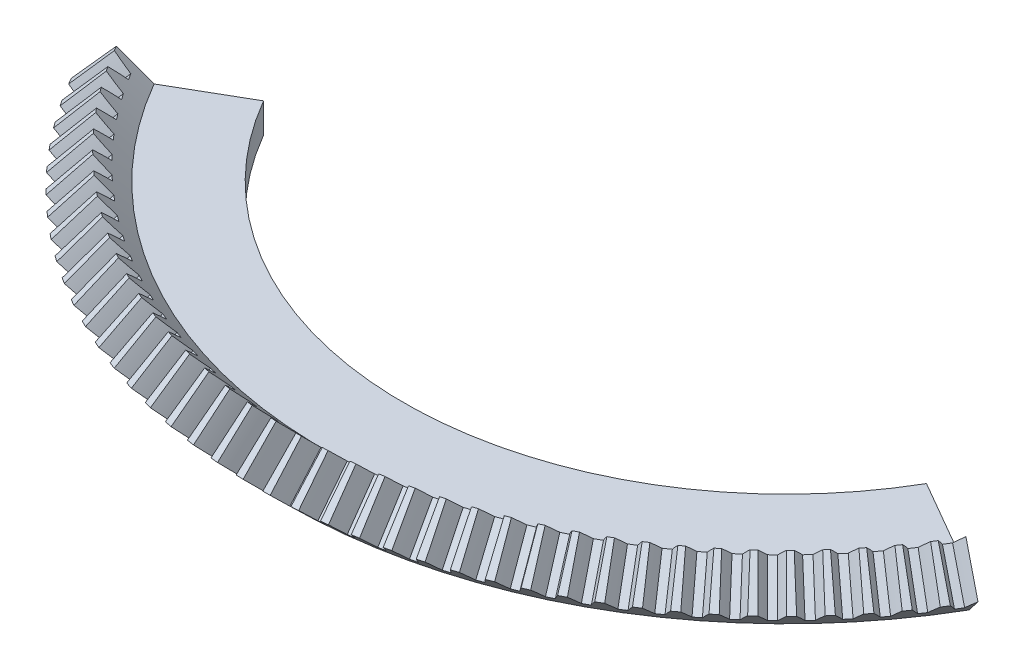
SolidWorks part; units mm, degrees
ref_plane "Front Plane" through (0, 0, 0) normal (0, 0, 1) x (1, 0, 0)
ref_plane "Top Plane" through (0, 0, 0) normal (0, 1, 0) x (1, 0, 0)
ref_plane "Right Plane" through (0, 0, 0) normal (1, 0, 0) x (0, 0, -1)
sketch "Sketch11" plane through (0, 0, 0) normal (0, 0, 1) x (1, 0, 0)
  line L0 (0, 0) -> (0, 120) construction
  line L1 (0, 0) -> (-90, 0) construction
  line L2 (0, 0) -> (0, -49.4819) construction
  line L3 (0, -49.4819) -> (-91.0605, -49.4819) construction
  line L4 (0, -79.9822) -> (-88.82, -79.9822) construction
  line L5 (-90, 120) -> (0.0147, 210.0147) construction
  line L6 (-90, 120) -> (-61.5021, 120) construction
  line L7 (0.0147, 210.0147) -> (-96.0377, 116.1829) construction
  line L8 (0.0147, 210.0147) -> (-92.7643, 115.0069) construction
  line L9 (0.0147, 210.0147) -> (0.0147, 146.7224) construction
  line L10 (-90, 120) -> (-88.9191, 118.9445)
  line L11 (-90, 120) -> (-91.0402, 121.0648)
  line L12 (-91.0402, 121.0648) -> (-85.3176, 126.6551)
  line L13 (-85.3176, 126.6551) -> (-83.3068, 124.6916)
  line L14 (-83.3068, 124.6916) -> (-88.9191, 118.9445)
  line L15 (-88.9191, 118.9445) -> (-81.7646, 111.9578)
  line L16 (-81.7646, 111.9578) -> (0, 111.9578)
  line L17 (-83.3068, 124.6916) -> (-78.6153, 120)
  line L18 (-78.6153, 120) -> (0, 120)
  line L19 (0, 120) -> (0, 111.9578)
  dimension "D1" = 90
  dimension "D2" = 91.0605
  dimension "D3" = 88.82
  dimension "D4" = 45
  dimension "D5" = 127.3
  dimension "D6" = 45.67
  dimension "D7" = 44.32
revolve "Revolve1" add sketch "Sketch11" angle 360 about L0
sketch "Sketch12" plane through (0, 0, 0) normal (1, 0, 0) x (0, 0, -1)
  line L0 (-88.9191, 118.9445) -> (0, 207.8636) construction
  line L1 (0, 111.9578) -> (0, 207.8636) construction
  line L2 (-81.7646, 111.9578) -> (81.7646, 111.9578) construction
  line L3 (-88.9191, 118.9445) -> (22.2775, 118.9445) construction
  line L4 (88.9191, 118.9445) -> (-88.9191, 118.9445) construction
  dimension "D1" = 45
sketch "Sketch13" plane through (0, 111.9578, 0) normal (0, -1, 0) x (1, 0, 0)
  line L0 (0, 81.7646) -> (-67.0377, 81.7646) construction
  circle A0 centre (0, 0) radius 81.7646 construction
ref_plane "Plane2" through (0, 16.4367, -16.0511) normal (0, 0.7154, -0.6987) x (1, 0, 0)
sketch "Sketch14" plane through (0, 16.4367, -16.0511) normal (0, 0.7154, -0.6987) x (1, 0, 0)
  arc A1 (-1.0406, -143.4694) -> (0, -146.7194) centre (40.9134, -131.8281) ccw
  arc A2 (-2.2935, -143.4526) -> (-3.4211, -146.6734) centre (-43.9195, -130.688) cw
  arc A3 (-3.4211, -146.6734) -> (0, -146.7194) centre (0, -19.4194) ccw
  arc A4 (-2.2935, -143.4526) -> (-1.0406, -143.4694) centre (0, -19.4194) ccw
  point P1 (0, 0)
ref_plane "Plane3" through (0, 107.5134, -104.9912) normal (0, 0.7154, -0.6987) x (1, 0, 0)
sketch "Sketch15" plane through (0, 107.5134, -104.9912) normal (0, 0.7154, -0.6987) x (1, 0, 0)
  circle A0 centre (0, -145.2557) radius 0.05
extrude "Cut-Extrude1" cut sketch "Sketch14" along normal blind 12
pattern_circular "CirPattern1" count 120 over 360 about axis through (0, 118.9445, 0) along (0, -1, 0) of "Cut-Extrude1"
sketch "Sketch17" plane through (0, 111.9578, 0) normal (0, -1, 0) x (1, 0, 0)
  circle A0 centre (0, 0) radius 90
extrude "Cut-Extrude4" cut sketch "Sketch17" against normal blind 3
sketch "Sketch18" plane through (0, 120, 0) normal (0, 1, 0) x (1, 0, 0)
  line L0 (-78.6153, 0) -> (99.4644, 0)
  line L1 (99.4644, 0) -> (99.4644, 123.9381)
  line L2 (99.4644, 123.9381) -> (-125.0006, 123.9381)
  line L3 (-125.0006, 123.9381) -> (-125.0006, 0)
  line L4 (-125.0006, 0) -> (-78.6153, 0)
  circle A0 centre (0, 0) radius 78.6153 construction
extrude "Cut-Extrude8" cut sketch "Sketch18" against normal blind 42 and the other way blind 74
sketch "Sketch20" plane through (0, 120, 0) normal (0, 1, 0) x (1, 0, 0)
  circle A0 centre (0, 0) radius 65
extrude "Cut-Extrude9" cut sketch "Sketch20" against normal blind 42
sketch "Sketch21" plane through (0, 120, 0) normal (0, 1, 0) x (1, 0, 0)
  line L0 (0, 0) -> (-94.2687, -54.4261)
  line L2 (0, 0) -> (-43.355, 0) construction
  line L3 (0, 0) -> (40.0116, 0) construction
  line L4 (-94.2687, -54.4261) -> (-137.9055, 21.155)
  line L5 (-137.9055, 21.155) -> (-72.4742, 58.9318)
  line L6 (-72.4742, 58.9318) -> (-28.8374, -16.6493)
  arc M1 (65, 0) -> (-65, 0) centre (0, 0) cw
  line M2 (-65, 0) -> (-78.6153, 0)
  arc M3 (-78.6153, 0) -> (78.6153, 0) centre (0, 0) ccw
  dimension "D1" = 30
extrude "Cut-Extrude11" cut sketch "Sketch21" along normal blind 47 and the other way blind 67 contours L6 L5 L4 L0 M3 M2 M1
sketch "Sketch22" plane through (0, 120, 0) normal (0, 1, 0) x (1, 0, 0)
  line L0 (24.3569, -14.0625) -> (93.3239, -53.8806)
  line L1 (0, 0) -> (44.0283, 0) construction
  line L2 (93.3239, -53.8806) -> (124.2396, -8.7618)
  line L3 (124.2396, -8.7618) -> (58.741, 36.1182)
  line L4 (58.741, 36.1182) -> (24.3569, -14.0625)
  dimension "D1" = 30
extrude "Cut-Extrude13" cut sketch "Sketch22" along normal blind 34 and the other way blind 56
sketch "Sketch23" plane through (0, 120, 0) normal (0, 1, 0) x (1, 0, 0)
  line L0 (-38.7517, -22.3733) -> (-92.4341, -53.3668)
  line L1 (0, 0) -> (-27.7753, 0) construction
  line L2 (-92.4341, -53.3668) -> (-128.3692, 8.8746)
  line L3 (-128.3692, 8.8746) -> (-70.1997, 38.7855)
  line L4 (-70.1997, 38.7855) -> (-38.7517, -22.3733)
  dimension "D1" = 30
extrude "Cut-Extrude14" cut sketch "Sketch23" along normal blind 36 and the other way blind 69
